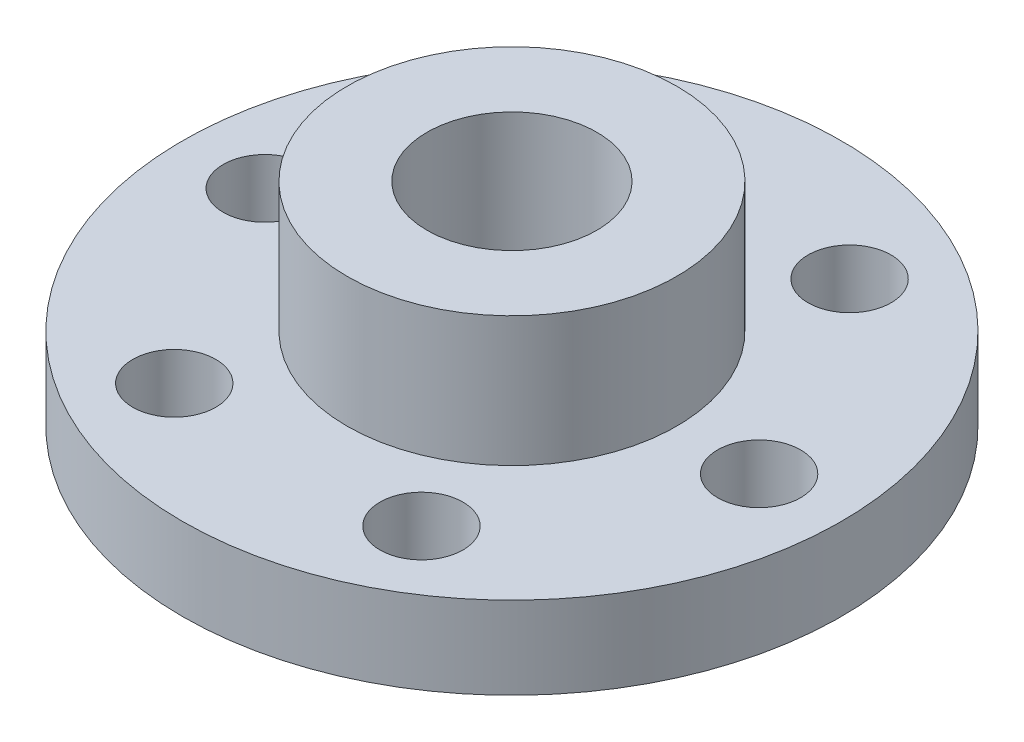
SolidWorks part; units mm, degrees
ref_plane "Front Plane" through (0, 0, 0) normal (0, 0, 1) x (1, 0, 0)
ref_plane "Top Plane" through (0, 0, 0) normal (0, 1, 0) x (1, 0, 0)
ref_plane "Right Plane" through (0, 0, 0) normal (1, 0, 0) x (0, 0, -1)
sketch "Sketch1" plane through (0, 0, 0) normal (0, 1, 0) x (1, 0, 0)
  line L0 (0, 0) -> (6.5484, 0) construction
  line L4 (0, 0) -> (-19.05, 0) construction
  circle A0 centre (0, 0) radius 4.826
  circle A1 centre (0, 0) radius 6.5484 construction
  arc A2 (3.9286, 10.8597) -> (3.9286, -10.8597) centre (0, 0) ccw construction
  circle A3 centre (0, 0) radius 25.4
  circle A5 centre (0, 0) radius 11.5484 construction
  circle A6 centre (-19.05, 0) radius 2.9766 construction
  dimension "D1" = 9.652
  dimension "D2" = 13.0969
  dimension "D3" = 23.0969
  dimension "D7" = 5.9531
  dimension "D5" = 50.8
  dimension "D4" = 19.05
extrude "main body" add sketch "Sketch1" along normal blind 6.35
sketch "Sketch2" plane through (0, 6.35, 0) normal (0, 1, 0) x (1, 0, 0)
  circle A0 centre (0, 0) radius 12.7
  circle A2 centre (0, 0) radius 6.5484
  dimension "D1" = 13.0969
  dimension "D2" = 25.4
extrude "tap boss" add sketch "Sketch2" along normal blind 10
hole_wizard "M6 Clearance Hole1" positions "Sketch3" profile "Sketch4" hole size "M6" standard "ANSI Metric" end condition through all
sketch "Sketch3" plane through (0, 6.35, 0) normal (0, 1, 0) x (1, 0, 0)
  point P0 (-19.05, 0)
  point P7 (-9.525, 16.4978)
  point P8 (9.525, 16.4978)
  point P9 (19.05, 0)
  point P10 (9.525, -16.4978)
  point P11 (-9.525, -16.4978)
  point P12 (0, 0)
  dimension "D1" = 6
sketch "Sketch4" plane through (-19.05, 6.35, 0) normal (1, 0, 0) x (0, 0, 1)
  line L0 (0, 0) -> (0, 6.35)
  line L1 (0, 6.35) -> (3.2, 6.35)
  line L2 (3.2, 6.35) -> (3.2, 0)
  line L5 (3.2, 0) -> (0, 0)
  line L11 (0, -6.35) -> (0, 107.95) construction
  dimension "Thru Hole Dia." = 6.4
  dimension "Thru Hole Depth" = 6.35
sketch "Sketch5" plane through (0, 0, 0) normal (0, -1, 0) x (1, 0, 0)
  line L0 (0, 0) -> (-25.4, 0) construction
  line L1 (-25.4, 0) -> (-25.4, 25.4) construction
  line L2 (-25.4, 25.4) -> (0, 25.4) construction
  line L3 (0, 25.4) -> (0, 0) construction
  circle A0 centre (0, 0) radius 25.4 construction
  point P6 (0, 0)
  point P9 (0, 0)
  point P10 (0, 0)
  point P11 (0, 0)
  point P12 (0, 0)
equation "\"z\" = 8\t\t\t\t'number of blades"
equation "\"de\" = 0.43in\t\t\t'entrance eye diameter"
equation "\"de_length\" = 4mm\t\t'entrance eye consistent length"
equation "\"d_exit\" = 0.18in \t\t'throat aka d1"
equation "\"d2\" = 2.1in \t\t\t'outer diameter of the impeller"
equation "\"b2\" = .2in\t\t\t'tip height from disc surface at d2; slightly higher than d_exit"
equation "\"b1\" = \"b2\" + (\"d2\"/2 - \"de\"/2)*tan(\"theta\") \t\t\t'tip height from disc surface at inlet eye"
equation "\"theta\" = 12\t\t\t'angle of blades from inner to outer "
equation "\"ae\" = 3.14*(\"de\"^2)/4\t\t'entrance eye area'"
equation "\"ce\" = 3.14*\"de\"\t\t'entrance eye circumference"
equation "\"av_ratio\" = .325\t\t'ratio of av/ae at N_s of 470, range is .275 to .375, .325 ideal. High ratio means bigger area means smaller blades"
equation "\"av\" = \"ae\"*\"av_ratio\"\t\t'area between just two blades"
equation "\"s_open\" = \"av\"/\"b1\"\t\t'width of open area"
equation "\"s\"=\"ce\" - \"z\"*\"s_open\""
equation "\"min blade thickness\" = .15in"
equation "\"bearing OD\" = 30mm"
equation "\"bearing ID\"= 10mm"
equation "\"bearing depth\"= 9mm"
equation "\"bearing outer race thickness\"= 1mm"
equation "\"bearing inner race thickness\"= 1mm"
equation "\"bearing bore\" = \"bearing depth\" + 1mm"
equation "\"lower seal OD\" = .917in\t\t'this is https://www.mcmaster.com/#9281k121/=174001b"
equation "\"lower seal ID\"= .375in"
equation "\"lower seal depth\" = .625in + .218in"
equation "\"lower seal bore\" = \"lower seal depth\" + 1mm"
equation "\"upper seal OD\" = 1.125in\t'this is https://www.mcmaster.com/#5154t33/=173zuau, needs to be visually inspected before machining!"
equation "\"upper seal ID\"= 0.625in"
equation "\"upper seal depth\"= .25in\t'aka height; these values need to be confirmed by inspection!! We may want to compress the height."
equation "\"upper seal bore\" = \"upper seal depth\" + 1mm"
equation "\"big o-ring thickness\" = .139in"
equation "\"big o-ring OD\" = 2.734in"
equation "\"big o-ring ID\" = 3.012in"
equation "\"big o-ring groove depth\" = \"big o-ring thickness\"*4/5"
equation "\"impeller center height\" = \"impeller base thickness\" + \"b1\"\t'impeller height at de"
equation "\"impeller outer height\" = \"impeller base thickness\" + \"b2\"\t'impeller height at de"
equation "\"impeller upper clearance\"= .5mm"
equation "\"impeller horizontal clearance\"= (\"d2\"*1.15 - \"d2\")/2 \t\t'clearance based on D2-D3 ratio for circular volute, ranges 1.15 to 1.2"
equation "\"impeller bottom clearance\"= .5mm"
equation "\"impeller base thickness\"= 2mm"
equation "\"impeller dowel diameter\" = 2mm"
equation "\"impeller bolt head diameter\" = \"m4 head bore diameter\""
equation "\"impeller bolt head depth\" = 4mm"
equation "\"impeller bolt stop depth\" = 3mm"
equation "\"impeller bolt bore\" = \"m4 clearance\""
equation "\"impeller shaft bore depth\" = 12mm"
equation "\"impeller shaft bore\" = 8mm"
equation "\"impeller boss depth\" = \"impeller shaft bore depth\"+\"impeller bolt stop depth\"+\"impeller bolt head depth\"-\"impeller base thickness\""
equation "\"impeller boss diameter\" = \"upper seal ID\""
equation "\"impeller dowel length\" = 2mm*2 + \"impeller shaft bore\""
equation "\"coupler motor shaft hole ID\"= 8mm"
equation "\"coupler OD\"= 17mm"
equation "\"coupler length\"= 25mm"
equation "\"motor OD\" = 64mm"
equation "\"motor shaft diameter\"= 8mm"
equation "\"motor shaft pride\"= 32mm"
equation "\"motor to bearing plate distance\" = \"motor shaft pride\" + 2mm +\"coupler length\"/2"
equation "\"square plate bolt bore\" = \"m8 clearance\""
equation "\"square plate bolt head diameter\" = 13.5mm"
equation "\"square plate bolt head depth\" = 8mm"
equation "\"square plate bolt pattern diameter\"= 3.5in"
equation "\"motor mount center bore\"= \"coupler OD\"+ 4mm"
equation "\"motor mount post radius\"= ( 3 * \"square plate bolt bore\" ) / 2"
equation "\"motor mount m4 screw hole diameter\"= 4mm"
equation "\"motor mount m4 head diameter\"= 7.25mm"
equation "\"motor mount m4 head depth\"= 4mm"
equation "\"motor mount m4 pattern diamater\" = 30mm"
equation "\"motor mount plate thickness\"= 8mm + \"motor mount m4 head depth\""
equation "\"bearing plate stop ID\" = \"bearing OD\" - 4mm"
equation "\"bearing plate stop depth\" = 3mm"
equation "\"bearing plate thickness\" = \"bearing bore\" + \"bearing plate stop depth\" + \"shaft bearing stop length\""
equation "\"lower seal plate lip depth\" = 2mm"
equation "\"lower seal plate lip ID\" = \"lower seal OD\" - 3mm"
equation "\"lower seal plate thickness\" = \"lower seal plate lip depth\" + \"lower seal bore\""
equation "\"shaft coupler section diameter\" = 8mm"
equation "\"shaft coupler section length\" = \"motor to bearing plate distance\" - \"motor shaft pride\" - 2mm"
equation "\"shaft bearing section diameter\" = \"bearing ID\""
equation "\"shaft bearing section length\" = \"bearing plate stop depth\" + \"bearing depth\""
equation "\"shaft bearing stop diameter\" = \"bearing ID\" + 4mm"
equation "\"shaft bearing stop length\" = 3mm"
equation "\"shaft lower seal section diameter\" = \"lower seal ID\""
equation "\"shaft lower seal section length\" = \"lower seal plate thickness\" + 1mm"
equation "\"shaft impeller section diameter\" = \"impeller shaft bore\""
equation "\"shaft impeller section length\" = \"upper seal plate thickness\" + \"upper seal plate riser\" + \"impeller bottom clearance\" + \"impeller base thickness\" - \"impeller bolt head depth\" - \"impeller bolt stop depth\""
equation "\"upper seal plate thickness\" = \"upper seal plate pressure hole diameter\"+10mm"
equation "\"upper seal plate lip ID\" = \"upper seal OD\" - 3mm"
equation "\"upper seal plate riser\" = 6.59mm \t\t'this number needs to be read from the housing file"
equation "\"upper seal plate pressure hole diameter\" = .125in\t'this is 1/8 drill "
equation "\"upper seal plate pressure tap diameter\" = .328125in \t'this is 21/64 drill for a 1/8 ANPT tap"
equation "\"upper seal plate pressure tap grip\" = 5mm\t\t'this is the area around the tap so it doesn't crack"
equation "\"upper seal plate pressure tap depth\" = 12mm"
equation "\"impeller cavity center height\"= \"impeller bottom clearance\" + \"impeller upper clearance\" + \"impeller center height\""
equation "\"impeller cavity diameter\"= 2 * \"impeller horizontal clearance\" + \"d2\" \t\t\t\t\t\t\t\t\t'called D3 analytically"
equation "\"impeller cavity outer height\"= \"impeller bottom clearance\" + \"impeller upper clearance\" + \"impeller base thickness\" + \"b2\" \t\t'this is height at impeller diameter d2, not at d3"
equation "\"impeller housing thickness\"= \"impeller housing exit threaded diameter\" + 2*\"impeller housing outlet grip\""
equation "\"impeller housing diameter\" = 4.5in"
equation "\"impeller housing bolt count\" = 8"
equation "\"impeller housing bolt diameter\" = \"m6 clearance\""
equation "\"impeller housing bolt pattern diameter\" = 3.5in"
equation "\"impeller housing threaded inlet diameter\" = 0.71875in \t'this is the 23/32 drill size for 1/2 NPT fitting https://www.mcmaster.com/#50715k269/=176pljy"
equation "\"impeller housing threaded inlet depth\"= .6in"
equation "\"impeller housing exit threaded diameter\"= 0.515625in \t\t'this is the 33/64 drill size for 9/16-18 fitting, expecting swagelok SS-8FK0-1-6STH fitting"
equation "\"impeller housing exit threaded depth\"= 10mm"
equation "\"impeller housing diffuser conical angle\"=10"
equation "\"impeller housing diffuser tangent angle\"=5"
equation "\"impeller housing diffuser final diameter\" = .38in\t\t'aka d2'"
equation "\"impeller housing outlet grip\" = 5mm"
equation "\"end mill size\" = 0.375in\t'for 3/8 endmill"
equation "\"m4 clearance\" = 0.171875in \t'this is 11/64 bit for 4.36mm"
equation "\"m4 tap\" = 0.125in\t\t'this is 1/8 bit for 3.17mm"
equation "\"m4 head bore diameter\" = 7.5mm"
equation "\"m4 head bore depth\" = 5mm\t'actual is ~4mm"
equation "\"m6 clearance\" = 0.234375in\t'this is 15/64 bit = 5.95mm, could use 6mm bit, B bit for 6.04mm or 1/4 bit for 6.35mm"
equation "\"m6 tap\" = 5mm\t\t\t'5mm is appropriate, could use 13/64 or #5,6,7"
equation "\"m6 head bore diameter\" = 11mm\t\t"
equation "\"m6 head bore depth\" = 7mm\t'actual is 6mm"
equation "\"m8 clearance\" = 0.3125in\t'this is 5/16in for 7.93mm, could use 8mm, O,P, or 21/64"
equation "\"m8 tap\" = 0.265625in\t\t'this is 17/64 for 6.746875mm"
equation "\"m8 head bore diameter\" = 14mm"
equation "\"m8 head bore depth\" = 9mm\t'actual is 8mm"
equation "\"D1@Sketch1\"=\"impeller housing diffuser final diameter\""
equation "\"D2@Sketch1\"=\"impeller housing exit threaded diameter\""
equation "\"D3@Sketch1\"=\"impeller housing exit threaded diameter\"+\"impeller housing outlet grip\"*2 "
equation "\"D7@Sketch1\"=\"m6 clearance\""
equation "\"D1@Sketch2\"=\"impeller housing exit threaded diameter\""
equation "\"D1@tap boss\"=10mm"
equation "\"diffuser cartridge OD\" =.75in"
equation "\"diffuser flange bolt pattern diameter\" = 1.4in"
equation "\"D4@Sketch1\"=.75in"
